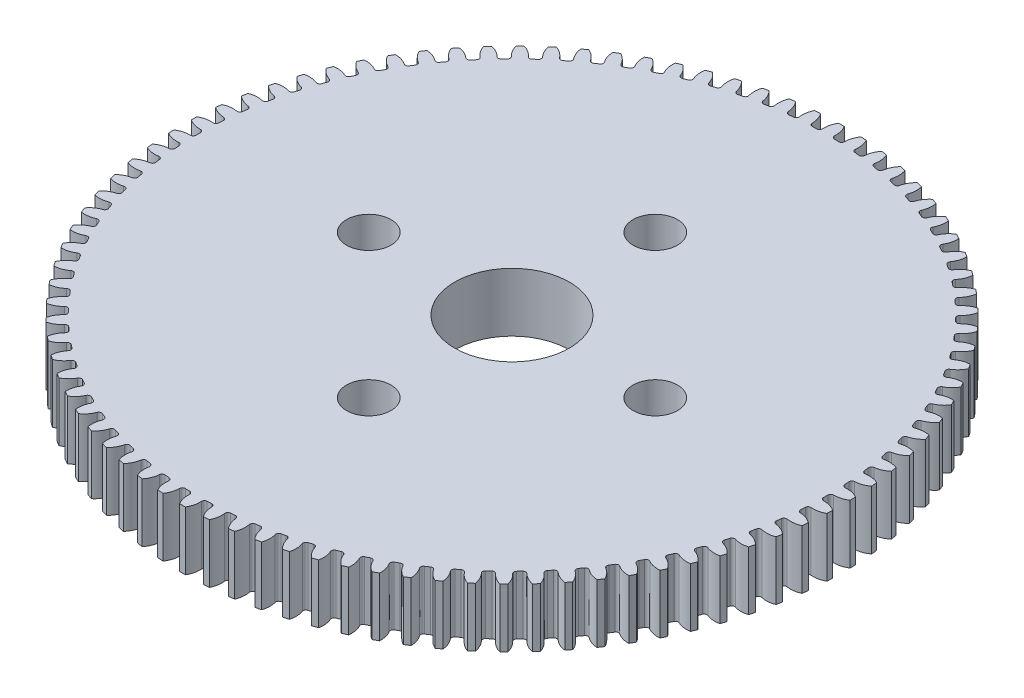
SolidWorks part; units mm, degrees
ref_plane "Front Plane" through (0, 0, 0) normal (0, 0, 1) x (1, 0, 0)
ref_plane "Top Plane" through (0, 0, 0) normal (0, 1, 0) x (1, 0, 0)
ref_plane "Right Plane" through (0, 0, 0) normal (1, 0, 0) x (0, 0, -1)
sketch "Sketch1" plane through (0, 0, 0) normal (0, 1, 0) x (1, 0, 0)
  line L0 (0, 0) -> (0, 23) construction
  line L2 (-0.1965, 23) -> (0.1965, 23)
  line L5 (1.4084, 22.9577) -> (1.8004, 22.9303)
  line L6 (3.0064, 22.8035) -> (3.3956, 22.7488)
  line L7 (4.5898, 22.5382) -> (4.9742, 22.4565)
  line L8 (6.1508, 22.1632) -> (6.5285, 22.0549)
  line L9 (7.6818, 21.6801) -> (8.0511, 21.5457)
  line L10 (9.1754, 21.0915) -> (9.5345, 20.9316)
  line L11 (10.6243, 20.4) -> (10.9713, 20.2155)
  line L12 (12.0215, 19.6092) -> (12.3548, 19.401)
  line L13 (13.3601, 18.7229) -> (13.678, 18.4919)
  line L14 (14.6336, 17.7453) -> (14.9346, 17.4927)
  line L15 (15.8358, 16.6813) -> (16.1185, 16.4083)
  line L16 (16.9608, 15.536) -> (17.2238, 15.244)
  line L17 (18.0033, 14.3151) -> (18.2452, 14.0054)
  line L18 (18.958, 13.0243) -> (19.1777, 12.6985)
  line L19 (19.8203, 11.6702) -> (20.0168, 11.3298)
  line L20 (20.5861, 10.2591) -> (20.7584, 9.9059)
  line L21 (21.2516, 8.7981) -> (21.3988, 8.4338)
  line L22 (21.8136, 7.2943) -> (21.935, 6.9205)
  line L23 (22.2693, 5.7549) -> (22.3643, 5.3735)
  line L24 (22.6165, 4.1874) -> (22.6847, 3.8004)
  line L25 (22.8535, 2.5996) -> (22.8945, 2.2087)
  line L26 (22.9791, 0.9991) -> (22.9928, 0.6063)
  line L27 (22.9928, -0.6063) -> (22.9791, -0.9991)
  line L28 (22.8945, -2.2087) -> (22.8535, -2.5996)
  line L29 (22.6847, -3.8004) -> (22.6165, -4.1874)
  line L30 (22.3643, -5.3735) -> (22.2693, -5.7549)
  line L31 (21.935, -6.9205) -> (21.8136, -7.2943)
  line L32 (21.3988, -8.4338) -> (21.2516, -8.7981)
  line L33 (20.7584, -9.9059) -> (20.5861, -10.2591)
  line L34 (20.0168, -11.3298) -> (19.8203, -11.6702)
  line L35 (19.1777, -12.6985) -> (18.958, -13.0243)
  line L36 (18.2452, -14.0054) -> (18.0033, -14.3151)
  line L37 (17.2238, -15.244) -> (16.9608, -15.536)
  line L38 (16.1185, -16.4083) -> (15.8358, -16.6813)
  line L39 (14.9346, -17.4927) -> (14.6336, -17.7453)
  line L40 (13.678, -18.4919) -> (13.3601, -18.7229)
  line L41 (12.3548, -19.401) -> (12.0215, -19.6092)
  line L42 (10.9713, -20.2155) -> (10.6243, -20.4)
  line L43 (9.5345, -20.9316) -> (9.1754, -21.0915)
  line L44 (8.0511, -21.5457) -> (7.6818, -21.6801)
  line L45 (6.5285, -22.0549) -> (6.1508, -22.1632)
  line L46 (4.9742, -22.4565) -> (4.5898, -22.5382)
  line L47 (3.3956, -22.7488) -> (3.0064, -22.8035)
  line L48 (1.8004, -22.9303) -> (1.4084, -22.9577)
  line L49 (0.1965, -23) -> (-0.1965, -23)
  line L50 (-1.4084, -22.9577) -> (-1.8004, -22.9303)
  line L51 (-3.0064, -22.8035) -> (-3.3956, -22.7488)
  line L52 (-4.5898, -22.5382) -> (-4.9742, -22.4565)
  line L53 (-6.1508, -22.1632) -> (-6.5285, -22.0549)
  line L54 (-7.6818, -21.6801) -> (-8.0511, -21.5457)
  line L55 (-9.1754, -21.0915) -> (-9.5345, -20.9316)
  line L56 (-10.6243, -20.4) -> (-10.9713, -20.2155)
  line L57 (-12.0215, -19.6092) -> (-12.3548, -19.401)
  line L58 (-13.3601, -18.7229) -> (-13.678, -18.4919)
  line L59 (-14.6336, -17.7453) -> (-14.9346, -17.4927)
  line L60 (-15.8358, -16.6813) -> (-16.1185, -16.4083)
  line L61 (-16.9608, -15.536) -> (-17.2238, -15.244)
  line L62 (-18.0033, -14.3151) -> (-18.2452, -14.0054)
  line L63 (-18.958, -13.0243) -> (-19.1777, -12.6985)
  line L64 (-19.8203, -11.6702) -> (-20.0168, -11.3298)
  line L65 (-20.5861, -10.2591) -> (-20.7584, -9.9059)
  line L66 (-21.2516, -8.7981) -> (-21.3988, -8.4338)
  line L67 (-21.8136, -7.2943) -> (-21.935, -6.9205)
  line L68 (-22.2693, -5.7549) -> (-22.3643, -5.3735)
  line L69 (-22.6165, -4.1874) -> (-22.6847, -3.8004)
  line L70 (-22.8535, -2.5996) -> (-22.8945, -2.2087)
  line L71 (-22.9791, -0.9991) -> (-22.9928, -0.6063)
  line L72 (-22.9928, 0.6063) -> (-22.9791, 0.9991)
  line L73 (-22.8945, 2.2087) -> (-22.8535, 2.5996)
  line L74 (-22.6847, 3.8004) -> (-22.6165, 4.1874)
  line L75 (-22.3643, 5.3735) -> (-22.2693, 5.7549)
  line L76 (-21.935, 6.9205) -> (-21.8136, 7.2943)
  line L77 (-21.3988, 8.4338) -> (-21.2516, 8.7981)
  line L78 (-20.7584, 9.9059) -> (-20.5861, 10.2591)
  line L79 (-20.0168, 11.3298) -> (-19.8203, 11.6702)
  line L80 (-19.1777, 12.6985) -> (-18.958, 13.0243)
  line L81 (-18.2452, 14.0054) -> (-18.0033, 14.3151)
  line L82 (-17.2238, 15.244) -> (-16.9608, 15.536)
  line L83 (-16.1185, 16.4083) -> (-15.8358, 16.6813)
  line L84 (-14.9346, 17.4927) -> (-14.6336, 17.7453)
  line L85 (-13.678, 18.4919) -> (-13.3601, 18.7229)
  line L86 (-12.3548, 19.401) -> (-12.0215, 19.6092)
  line L87 (-10.9713, 20.2155) -> (-10.6243, 20.4)
  line L88 (-9.5345, 20.9316) -> (-9.1754, 21.0915)
  line L89 (-8.0511, 21.5457) -> (-7.6818, 21.6801)
  line L90 (-6.5285, 22.0549) -> (-6.1508, 22.1632)
  line L91 (-4.9742, 22.4565) -> (-4.5898, 22.5382)
  line L92 (-3.3956, 22.7488) -> (-3.0064, 22.8035)
  line L93 (-1.8004, 22.9303) -> (-1.4084, 22.9577)
  circle A0 centre (0, 0) radius 22.5 construction
  circle A1 centre (0, 0) radius 4
  arc A3 (-0.6132, 21.8914) -> (-0.9154, 21.8809) centre (0, 0) ccw
  arc A4 (-0.4192, 22.1039) -> (-0.1965, 23) centre (1.1086, 22.2) cw
  arc A5 (0.4192, 22.1039) -> (0.1965, 23) centre (-1.1086, 22.2) ccw
  arc A6 (-0.4192, 22.1039) -> (-0.6132, 21.8914) centre (-0.6188, 22.0913) cw
  arc A7 (0.6132, 21.8914) -> (0.4192, 22.1039) centre (0.6188, 22.0913) cw
  arc A8 (1.1237, 22.0793) -> (1.4084, 22.9577) centre (2.6545, 22.0686) cw
  arc A9 (1.1237, 22.0793) -> (0.9154, 21.8809) centre (0.9238, 22.0807) cw
  arc A10 (2.1387, 21.7953) -> (1.96, 22.0208) centre (2.1583, 21.9944) cw
  arc A11 (1.96, 22.0208) -> (1.8004, 22.9303) centre (0.4427, 22.2233) ccw
  arc A12 (2.6612, 21.9471) -> (3.0064, 22.8035) centre (4.1874, 21.8297) cw
  arc A13 (2.6612, 21.9471) -> (2.4395, 21.7637) centre (2.4618, 21.9625) cw
  arc A14 (3.6539, 21.593) -> (3.4914, 21.8304) centre (3.6873, 21.7902) cw
  arc A15 (3.4914, 21.8304) -> (3.3956, 22.7488) centre (1.9919, 22.1382) ccw
  arc A16 (4.1857, 21.708) -> (4.5898, 22.5382) centre (5.7, 21.4844) cw
  arc A17 (4.1857, 21.708) -> (3.9517, 21.5405) centre (3.9878, 21.7372) cw
  arc A18 (5.1513, 21.2855) -> (5.0057, 21.5337) centre (5.1983, 21.4799) cw
  arc A19 (5.0057, 21.5337) -> (4.9742, 22.4565) centre (3.5313, 21.9454) ccw
  arc A20 (5.6897, 21.3632) -> (6.1508, 22.1632) centre (7.1848, 21.0344) cw
  arc A21 (5.6897, 21.3632) -> (5.4447, 21.2124) centre (5.4944, 21.4061) cw
  arc A22 (6.6235, 20.8744) -> (6.4956, 21.1321) centre (6.684, 21.065) cw
  arc A23 (6.4956, 21.1321) -> (6.5285, 22.0549) centre (5.0535, 21.6456) ccw
  arc A24 (7.1661, 20.9142) -> (7.6818, 21.6801) centre (8.6346, 20.482) cw
  arc A25 (7.1661, 20.9142) -> (6.9111, 20.7809) centre (6.9742, 20.9707) cw
  arc A26 (8.0635, 20.3615) -> (7.9539, 20.6275) centre (8.1371, 20.5474) cw
  arc A27 (7.9539, 20.6275) -> (8.0511, 21.5457) centre (6.5511, 21.2403) ccw
  arc A28 (8.6075, 20.3634) -> (9.1754, 21.0915) centre (10.0423, 19.8298) cw
  arc A29 (8.6075, 20.3634) -> (8.3439, 20.2482) centre (8.4201, 20.4331) cw
  arc A30 (9.4642, 19.7494) -> (9.3734, 20.0224) centre (9.5506, 19.9298) cw
  arc A31 (9.3734, 20.0224) -> (9.5345, 20.9316) centre (8.0168, 20.7316) ccw
  arc A32 (10.007, 19.7134) -> (10.6243, 20.4) centre (11.4011, 19.081) cw
  arc A33 (10.007, 19.7134) -> (9.736, 19.6168) centre (9.8249, 19.796) cw
  arc A34 (10.8188, 19.0411) -> (10.7473, 19.3198) centre (10.9176, 19.215) cw
  arc A35 (10.7473, 19.3198) -> (10.9713, 20.2155) centre (9.4435, 20.1219) ccw
  arc A36 (11.3578, 18.9673) -> (12.0215, 19.6092) centre (12.7043, 18.2392) cw
  arc A37 (11.3578, 18.9673) -> (11.0807, 18.8899) centre (11.1819, 19.0624) cw
  arc A38 (12.1207, 18.24) -> (12.0688, 18.523) centre (12.2314, 18.4066) cw
  arc A39 (12.0688, 18.523) -> (12.3548, 19.401) centre (10.8241, 19.4141) ccw
  arc A40 (12.6532, 18.1288) -> (13.3601, 18.7229) centre (13.9457, 17.3086) cw
  arc A41 (12.6532, 18.1288) -> (12.3714, 18.0709) centre (12.4844, 18.236) cw
  arc A42 (13.3635, 17.3501) -> (13.3315, 17.636) centre (13.4856, 17.5086) cw
  arc A43 (13.3315, 17.636) -> (13.678, 18.4919) centre (12.152, 18.6118) ccw
  arc A44 (13.887, 17.202) -> (14.6336, 17.7453) centre (15.1191, 16.2936) cw
  arc A45 (13.887, 17.202) -> (13.6018, 17.1639) centre (13.726, 17.3207) cw
  arc A46 (14.5412, 16.3757) -> (14.5292, 16.6631) centre (14.674, 16.5252) cw
  arc A47 (14.5292, 16.6631) -> (14.9346, 17.4927) centre (13.4207, 17.7188) ccw
  arc A48 (15.0531, 16.1914) -> (15.8358, 16.6813) centre (16.2188, 15.1993) cw
  arc A49 (15.0531, 16.1914) -> (14.766, 16.1733) centre (14.9008, 16.321) cw
  arc A50 (15.6481, 15.3214) -> (15.6562, 15.609) centre (15.791, 15.4613) cw
  arc A51 (15.6562, 15.609) -> (16.1185, 16.4083) centre (14.624, 16.7394) ccw
  arc A52 (16.1459, 15.1019) -> (16.9608, 15.536) centre (17.2396, 14.0309) cw
  arc A53 (16.1459, 15.1019) -> (15.8582, 15.1039) centre (16.003, 15.2418) cw
  arc A54 (16.6788, 14.1925) -> (16.7069, 14.4789) centre (16.8311, 14.3222) cw
  arc A55 (16.7069, 14.4789) -> (17.2238, 15.244) centre (15.756, 15.6785) ccw
  arc A56 (17.16, 13.9388) -> (18.0033, 14.3151) centre (18.1763, 12.7941) cw
  arc A57 (17.16, 13.9388) -> (16.8732, 13.9609) centre (17.0273, 14.0884) cw
  arc A58 (17.6282, 12.9945) -> (17.6762, 13.2782) centre (17.7892, 13.1132) cw
  arc A59 (17.6762, 13.2782) -> (18.2452, 14.0054) centre (16.8113, 14.5412) ccw
  arc A60 (18.0906, 12.7078) -> (18.958, 13.0243) centre (19.0245, 11.495) cw
  arc A61 (18.0906, 12.7078) -> (17.8059, 12.7499) centre (17.9685, 12.8663) cw
  arc A62 (18.4917, 11.7332) -> (18.5594, 12.0128) centre (18.6606, 11.8403) cw
  arc A63 (18.5594, 12.0128) -> (19.1777, 12.6985) centre (17.7847, 13.3331) ccw
  arc A64 (18.933, 11.415) -> (19.8203, 11.6702) centre (19.78, 10.14) cw
  arc A65 (18.933, 11.415) -> (18.6519, 11.4767) centre (18.8223, 11.5815) cw
  arc A66 (19.2651, 10.4147) -> (19.3521, 10.6889) centre (19.441, 10.5098) cw
  arc A67 (19.3521, 10.6889) -> (20.0168, 11.3298) centre (18.6715, 12.06) ccw
  arc A68 (19.6831, 10.0665) -> (20.5861, 10.2591) centre (20.4392, 8.7355) cw
  arc A69 (19.6831, 10.0665) -> (19.4071, 10.1477) centre (19.5843, 10.2404) cw
  arc A70 (19.9447, 9.0455) -> (20.0506, 9.313) centre (20.1268, 9.1281) cw
  arc A71 (20.0506, 9.313) -> (20.7584, 9.9059) centre (19.4673, 10.7282) ccw
  arc A72 (20.3374, 8.6689) -> (21.2516, 8.7981) centre (20.9988, 7.2884) cw
  arc A73 (20.3374, 8.6689) -> (20.0677, 8.7692) centre (20.2509, 8.8493) cw
  arc A74 (20.5271, 7.6321) -> (20.6514, 7.8916) centre (20.7145, 7.7018) cw
  arc A75 (20.6514, 7.8916) -> (21.3988, 8.4338) centre (20.1682, 9.3441) ccw
  arc A76 (20.8925, 7.2291) -> (21.8136, 7.2943) centre (21.456, 5.8059) cw
  arc A77 (20.8925, 7.2291) -> (20.6305, 7.348) centre (20.8189, 7.4151) cw
  arc A78 (21.0095, 6.1817) -> (21.1516, 6.4318) centre (21.2013, 6.2381) cw
  arc A79 (21.1516, 6.4318) -> (21.935, 6.9205) centre (20.7709, 7.9145) ccw
  arc A80 (21.3459, 5.7541) -> (22.2693, 5.7549) centre (21.8088, 4.295) cw
  arc A81 (21.3459, 5.7541) -> (21.0928, 5.891) centre (21.2854, 5.9448) cw
  arc A82 (21.3895, 4.7011) -> (21.5487, 4.9407) centre (21.5848, 4.744) cw
  arc A83 (21.5487, 4.9407) -> (22.3643, 5.3735) centre (21.2724, 6.4463) ccw
  arc A84 (21.6953, 4.2511) -> (22.6165, 4.1874) centre (22.0552, 2.7633) cw
  arc A85 (21.6953, 4.2511) -> (21.4524, 4.4053) centre (21.6483, 4.4455) cw
  arc A86 (21.6653, 3.1975) -> (21.8409, 3.4255) centre (21.8632, 3.2268) cw
  arc A87 (21.8409, 3.4255) -> (22.6847, 3.8004) centre (21.6702, 4.9467) ccw
  arc A88 (21.939, 2.7274) -> (22.8535, 2.5996) centre (22.1943, 1.218) cw
  arc A89 (21.939, 2.7274) -> (21.7074, 2.8981) centre (21.9056, 2.9246) cw
  arc A90 (21.8356, 1.6785) -> (22.0266, 1.8936) centre (22.035, 1.6938) cw
  arc A91 (22.0266, 1.8936) -> (22.8945, 2.2087) centre (21.9625, 3.423) ccw
  arc A92 (22.0758, 1.1903) -> (22.9791, 0.9991) centre (22.2252, -0.3331) cw
  arc A93 (22.0758, 1.1903) -> (21.8567, 1.3768) centre (22.0563, 1.3894) cw
  arc A94 (21.8995, 0.1512) -> (22.1051, 0.3525) centre (22.0995, 0.1526) cw
  arc A95 (22.1051, 0.3525) -> (22.9928, 0.6063) centre (22.1478, 1.8827) ccw
  arc A96 (22.1051, -0.3525) -> (22.9928, -0.6063) centre (22.1478, -1.8827) cw
  arc A97 (22.1051, -0.3525) -> (21.8995, -0.1512) centre (22.0995, -0.1526) cw
  arc A98 (21.8567, -1.3768) -> (22.0758, -1.1903) centre (22.0563, -1.3894) cw
  arc A99 (22.0758, -1.1903) -> (22.9791, -0.9991) centre (22.2252, 0.3331) ccw
  arc A100 (22.0266, -1.8936) -> (22.8945, -2.2087) centre (21.9625, -3.423) cw
  arc A101 (22.0266, -1.8936) -> (21.8356, -1.6785) centre (22.035, -1.6938) cw
  arc A102 (21.7074, -2.8981) -> (21.939, -2.7274) centre (21.9056, -2.9246) cw
  arc A103 (21.939, -2.7274) -> (22.8535, -2.5996) centre (22.1943, -1.218) ccw
  arc A104 (21.8409, -3.4255) -> (22.6847, -3.8004) centre (21.6702, -4.9467) cw
  arc A105 (21.8409, -3.4255) -> (21.6653, -3.1975) centre (21.8632, -3.2268) cw
  arc A106 (21.4524, -4.4053) -> (21.6953, -4.2511) centre (21.6483, -4.4455) cw
  arc A107 (21.6953, -4.2511) -> (22.6165, -4.1874) centre (22.0552, -2.7633) ccw
  arc A108 (21.5487, -4.9407) -> (22.3643, -5.3735) centre (21.2724, -6.4463) cw
  arc A109 (21.5487, -4.9407) -> (21.3895, -4.7011) centre (21.5848, -4.744) cw
  arc A110 (21.0928, -5.891) -> (21.3459, -5.7541) centre (21.2854, -5.9448) cw
  arc A111 (21.3459, -5.7541) -> (22.2693, -5.7549) centre (21.8088, -4.295) ccw
  arc A112 (21.1516, -6.4318) -> (21.935, -6.9205) centre (20.7709, -7.9145) cw
  arc A113 (21.1516, -6.4318) -> (21.0095, -6.1817) centre (21.2013, -6.2381) cw
  arc A114 (20.6305, -7.348) -> (20.8925, -7.2291) centre (20.8189, -7.4151) cw
  arc A115 (20.8925, -7.2291) -> (21.8136, -7.2943) centre (21.456, -5.8059) ccw
  arc A116 (20.6514, -7.8916) -> (21.3988, -8.4338) centre (20.1682, -9.3441) cw
  arc A117 (20.6514, -7.8916) -> (20.5271, -7.6321) centre (20.7145, -7.7018) cw
  arc A118 (20.0677, -8.7692) -> (20.3374, -8.6689) centre (20.2509, -8.8493) cw
  arc A119 (20.3374, -8.6689) -> (21.2516, -8.7981) centre (20.9988, -7.2884) ccw
  arc A120 (20.0506, -9.313) -> (20.7584, -9.9059) centre (19.4673, -10.7282) cw
  arc A121 (20.0506, -9.313) -> (19.9447, -9.0455) centre (20.1268, -9.1281) cw
  arc A122 (19.4071, -10.1477) -> (19.6831, -10.0665) centre (19.5843, -10.2404) cw
  arc A123 (19.6831, -10.0665) -> (20.5861, -10.2591) centre (20.4392, -8.7355) ccw
  arc A124 (19.3521, -10.6889) -> (20.0168, -11.3298) centre (18.6715, -12.06) cw
  arc A125 (19.3521, -10.6889) -> (19.2651, -10.4147) centre (19.441, -10.5098) cw
  arc A126 (18.6519, -11.4767) -> (18.933, -11.415) centre (18.8223, -11.5815) cw
  arc A127 (18.933, -11.415) -> (19.8203, -11.6702) centre (19.78, -10.14) ccw
  arc A128 (18.5594, -12.0128) -> (19.1777, -12.6985) centre (17.7847, -13.3331) cw
  arc A129 (18.5594, -12.0128) -> (18.4917, -11.7332) centre (18.6606, -11.8403) cw
  arc A130 (17.8059, -12.7499) -> (18.0906, -12.7078) centre (17.9685, -12.8663) cw
  arc A131 (18.0906, -12.7078) -> (18.958, -13.0243) centre (19.0245, -11.495) ccw
  arc A132 (17.6762, -13.2782) -> (18.2452, -14.0054) centre (16.8113, -14.5412) cw
  arc A133 (17.6762, -13.2782) -> (17.6282, -12.9945) centre (17.7892, -13.1132) cw
  arc A134 (16.8732, -13.9609) -> (17.16, -13.9388) centre (17.0273, -14.0884) cw
  arc A135 (17.16, -13.9388) -> (18.0033, -14.3151) centre (18.1763, -12.7941) ccw
  arc A136 (16.7069, -14.4789) -> (17.2238, -15.244) centre (15.756, -15.6785) cw
  arc A137 (16.7069, -14.4789) -> (16.6788, -14.1925) centre (16.8311, -14.3222) cw
  arc A138 (15.8582, -15.1039) -> (16.1459, -15.1019) centre (16.003, -15.2418) cw
  arc A139 (16.1459, -15.1019) -> (16.9608, -15.536) centre (17.2396, -14.0309) ccw
  arc A140 (15.6562, -15.609) -> (16.1185, -16.4083) centre (14.624, -16.7394) cw
  arc A141 (15.6562, -15.609) -> (15.6481, -15.3214) centre (15.791, -15.4613) cw
  arc A142 (14.766, -16.1733) -> (15.0531, -16.1914) centre (14.9008, -16.321) cw
  arc A143 (15.0531, -16.1914) -> (15.8358, -16.6813) centre (16.2188, -15.1993) ccw
  arc A144 (14.5292, -16.6631) -> (14.9346, -17.4927) centre (13.4207, -17.7188) cw
  arc A145 (14.5292, -16.6631) -> (14.5412, -16.3757) centre (14.674, -16.5252) cw
  arc A146 (13.6018, -17.1639) -> (13.887, -17.202) centre (13.726, -17.3207) cw
  arc A147 (13.887, -17.202) -> (14.6336, -17.7453) centre (15.1191, -16.2936) ccw
  arc A148 (13.3315, -17.636) -> (13.678, -18.4919) centre (12.152, -18.6118) cw
  arc A149 (13.3315, -17.636) -> (13.3635, -17.3501) centre (13.4856, -17.5086) cw
  arc A150 (12.3714, -18.0709) -> (12.6532, -18.1288) centre (12.4844, -18.236) cw
  arc A151 (12.6532, -18.1288) -> (13.3601, -18.7229) centre (13.9457, -17.3086) ccw
  arc A152 (12.0688, -18.523) -> (12.3548, -19.401) centre (10.8241, -19.4141) cw
  arc A153 (12.0688, -18.523) -> (12.1207, -18.24) centre (12.2314, -18.4066) cw
  arc A154 (11.0807, -18.8899) -> (11.3578, -18.9673) centre (11.1819, -19.0624) cw
  arc A155 (11.3578, -18.9673) -> (12.0215, -19.6092) centre (12.7043, -18.2392) ccw
  arc A156 (10.7473, -19.3198) -> (10.9713, -20.2155) centre (9.4435, -20.1219) cw
  arc A157 (10.7473, -19.3198) -> (10.8188, -19.0411) centre (10.9176, -19.215) cw
  arc A158 (9.736, -19.6168) -> (10.007, -19.7134) centre (9.8249, -19.796) cw
  arc A159 (10.007, -19.7134) -> (10.6243, -20.4) centre (11.4011, -19.081) ccw
  arc A160 (9.3734, -20.0224) -> (9.5345, -20.9316) centre (8.0168, -20.7316) cw
  arc A161 (9.3734, -20.0224) -> (9.4642, -19.7494) centre (9.5506, -19.9298) cw
  arc A162 (8.3439, -20.2482) -> (8.6075, -20.3634) centre (8.4201, -20.4331) cw
  arc A163 (8.6075, -20.3634) -> (9.1754, -21.0915) centre (10.0423, -19.8298) ccw
  arc A164 (7.9539, -20.6275) -> (8.0511, -21.5457) centre (6.5511, -21.2403) cw
  arc A165 (7.9539, -20.6275) -> (8.0635, -20.3615) centre (8.1371, -20.5474) cw
  arc A166 (6.9111, -20.7809) -> (7.1661, -20.9142) centre (6.9742, -20.9707) cw
  arc A167 (7.1661, -20.9142) -> (7.6818, -21.6801) centre (8.6346, -20.482) ccw
  arc A168 (6.4956, -21.1321) -> (6.5285, -22.0549) centre (5.0535, -21.6456) cw
  arc A169 (6.4956, -21.1321) -> (6.6235, -20.8744) centre (6.684, -21.065) cw
  arc A170 (5.4447, -21.2124) -> (5.6897, -21.3632) centre (5.4944, -21.4061) cw
  arc A171 (5.6897, -21.3632) -> (6.1508, -22.1632) centre (7.1848, -21.0344) ccw
  arc A172 (5.0057, -21.5337) -> (4.9742, -22.4565) centre (3.5313, -21.9454) cw
  arc A173 (5.0057, -21.5337) -> (5.1513, -21.2855) centre (5.1983, -21.4799) cw
  arc A174 (3.9517, -21.5405) -> (4.1857, -21.708) centre (3.9878, -21.7372) cw
  arc A175 (4.1857, -21.708) -> (4.5898, -22.5382) centre (5.7, -21.4844) ccw
  arc A176 (3.4914, -21.8304) -> (3.3956, -22.7488) centre (1.9919, -22.1382) cw
  arc A177 (3.4914, -21.8304) -> (3.6539, -21.593) centre (3.6873, -21.7902) cw
  arc A178 (2.4395, -21.7637) -> (2.6612, -21.9471) centre (2.4618, -21.9625) cw
  arc A179 (2.6612, -21.9471) -> (3.0064, -22.8035) centre (4.1874, -21.8297) ccw
  arc A180 (1.96, -22.0208) -> (1.8004, -22.9303) centre (0.4427, -22.2233) cw
  arc A181 (1.96, -22.0208) -> (2.1387, -21.7953) centre (2.1583, -21.9944) cw
  arc A182 (0.9154, -21.8809) -> (1.1237, -22.0793) centre (0.9238, -22.0807) cw
  arc A183 (1.1237, -22.0793) -> (1.4084, -22.9577) centre (2.6545, -22.0686) ccw
  arc A184 (0.4192, -22.1039) -> (0.1965, -23) centre (-1.1086, -22.2) cw
  arc A185 (0.4192, -22.1039) -> (0.6132, -21.8914) centre (0.6188, -22.0913) cw
  arc A186 (-0.6132, -21.8914) -> (-0.4192, -22.1039) centre (-0.6188, -22.0913) cw
  arc A187 (-0.4192, -22.1039) -> (-0.1965, -23) centre (1.1086, -22.2) ccw
  arc A188 (-1.1237, -22.0793) -> (-1.4084, -22.9577) centre (-2.6545, -22.0686) cw
  arc A189 (-1.1237, -22.0793) -> (-0.9154, -21.8809) centre (-0.9238, -22.0807) cw
  arc A190 (-2.1387, -21.7953) -> (-1.96, -22.0208) centre (-2.1583, -21.9944) cw
  arc A191 (-1.96, -22.0208) -> (-1.8004, -22.9303) centre (-0.4427, -22.2233) ccw
  arc A192 (-2.6612, -21.9471) -> (-3.0064, -22.8035) centre (-4.1874, -21.8297) cw
  arc A193 (-2.6612, -21.9471) -> (-2.4395, -21.7637) centre (-2.4618, -21.9625) cw
  arc A194 (-3.6539, -21.593) -> (-3.4914, -21.8304) centre (-3.6873, -21.7902) cw
  arc A195 (-3.4914, -21.8304) -> (-3.3956, -22.7488) centre (-1.9919, -22.1382) ccw
  arc A196 (-4.1857, -21.708) -> (-4.5898, -22.5382) centre (-5.7, -21.4844) cw
  arc A197 (-4.1857, -21.708) -> (-3.9517, -21.5405) centre (-3.9878, -21.7372) cw
  arc A198 (-5.1513, -21.2855) -> (-5.0057, -21.5337) centre (-5.1983, -21.4799) cw
  arc A199 (-5.0057, -21.5337) -> (-4.9742, -22.4565) centre (-3.5313, -21.9454) ccw
  arc A200 (-5.6897, -21.3632) -> (-6.1508, -22.1632) centre (-7.1848, -21.0344) cw
  arc A201 (-5.6897, -21.3632) -> (-5.4447, -21.2124) centre (-5.4944, -21.4061) cw
  arc A202 (-6.6235, -20.8744) -> (-6.4956, -21.1321) centre (-6.684, -21.065) cw
  arc A203 (-6.4956, -21.1321) -> (-6.5285, -22.0549) centre (-5.0535, -21.6456) ccw
  arc A204 (-7.1661, -20.9142) -> (-7.6818, -21.6801) centre (-8.6346, -20.482) cw
  arc A205 (-7.1661, -20.9142) -> (-6.9111, -20.7809) centre (-6.9742, -20.9707) cw
  arc A206 (-8.0635, -20.3615) -> (-7.9539, -20.6275) centre (-8.1371, -20.5474) cw
  arc A207 (-7.9539, -20.6275) -> (-8.0511, -21.5457) centre (-6.5511, -21.2403) ccw
  arc A208 (-8.6075, -20.3634) -> (-9.1754, -21.0915) centre (-10.0423, -19.8298) cw
  arc A209 (-8.6075, -20.3634) -> (-8.3439, -20.2482) centre (-8.4201, -20.4331) cw
  arc A210 (-9.4642, -19.7494) -> (-9.3734, -20.0224) centre (-9.5506, -19.9298) cw
  arc A211 (-9.3734, -20.0224) -> (-9.5345, -20.9316) centre (-8.0168, -20.7316) ccw
  arc A212 (-10.007, -19.7134) -> (-10.6243, -20.4) centre (-11.4011, -19.081) cw
  arc A213 (-10.007, -19.7134) -> (-9.736, -19.6168) centre (-9.8249, -19.796) cw
  arc A214 (-10.8188, -19.0411) -> (-10.7473, -19.3198) centre (-10.9176, -19.215) cw
  arc A215 (-10.7473, -19.3198) -> (-10.9713, -20.2155) centre (-9.4435, -20.1219) ccw
  arc A216 (-11.3578, -18.9673) -> (-12.0215, -19.6092) centre (-12.7043, -18.2392) cw
  arc A217 (-11.3578, -18.9673) -> (-11.0807, -18.8899) centre (-11.1819, -19.0624) cw
  arc A218 (-12.1207, -18.24) -> (-12.0688, -18.523) centre (-12.2314, -18.4066) cw
  arc A219 (-12.0688, -18.523) -> (-12.3548, -19.401) centre (-10.8241, -19.4141) ccw
  arc A220 (-12.6532, -18.1288) -> (-13.3601, -18.7229) centre (-13.9457, -17.3086) cw
  arc A221 (-12.6532, -18.1288) -> (-12.3714, -18.0709) centre (-12.4844, -18.236) cw
  arc A222 (-13.3635, -17.3501) -> (-13.3315, -17.636) centre (-13.4856, -17.5086) cw
  arc A223 (-13.3315, -17.636) -> (-13.678, -18.4919) centre (-12.152, -18.6118) ccw
  arc A224 (-13.887, -17.202) -> (-14.6336, -17.7453) centre (-15.1191, -16.2936) cw
  arc A225 (-13.887, -17.202) -> (-13.6018, -17.1639) centre (-13.726, -17.3207) cw
  arc A226 (-14.5412, -16.3757) -> (-14.5292, -16.6631) centre (-14.674, -16.5252) cw
  arc A227 (-14.5292, -16.6631) -> (-14.9346, -17.4927) centre (-13.4207, -17.7188) ccw
  arc A228 (-15.0531, -16.1914) -> (-15.8358, -16.6813) centre (-16.2188, -15.1993) cw
  arc A229 (-15.0531, -16.1914) -> (-14.766, -16.1733) centre (-14.9008, -16.321) cw
  arc A230 (-15.6481, -15.3214) -> (-15.6562, -15.609) centre (-15.791, -15.4613) cw
  arc A231 (-15.6562, -15.609) -> (-16.1185, -16.4083) centre (-14.624, -16.7394) ccw
  arc A232 (-16.1459, -15.1019) -> (-16.9608, -15.536) centre (-17.2396, -14.0309) cw
  arc A233 (-16.1459, -15.1019) -> (-15.8582, -15.1039) centre (-16.003, -15.2418) cw
  arc A234 (-16.6788, -14.1925) -> (-16.7069, -14.4789) centre (-16.8311, -14.3222) cw
  arc A235 (-16.7069, -14.4789) -> (-17.2238, -15.244) centre (-15.756, -15.6785) ccw
  arc A236 (-17.16, -13.9388) -> (-18.0033, -14.3151) centre (-18.1763, -12.7941) cw
  arc A237 (-17.16, -13.9388) -> (-16.8732, -13.9609) centre (-17.0273, -14.0884) cw
  arc A238 (-17.6282, -12.9945) -> (-17.6762, -13.2782) centre (-17.7892, -13.1132) cw
  arc A239 (-17.6762, -13.2782) -> (-18.2452, -14.0054) centre (-16.8113, -14.5412) ccw
  arc A240 (-18.0906, -12.7078) -> (-18.958, -13.0243) centre (-19.0245, -11.495) cw
  arc A241 (-18.0906, -12.7078) -> (-17.8059, -12.7499) centre (-17.9685, -12.8663) cw
  arc A242 (-18.4917, -11.7332) -> (-18.5594, -12.0128) centre (-18.6606, -11.8403) cw
  arc A243 (-18.5594, -12.0128) -> (-19.1777, -12.6985) centre (-17.7847, -13.3331) ccw
  arc A244 (-18.933, -11.415) -> (-19.8203, -11.6702) centre (-19.78, -10.14) cw
  arc A245 (-18.933, -11.415) -> (-18.6519, -11.4767) centre (-18.8223, -11.5815) cw
  arc A246 (-19.2651, -10.4147) -> (-19.3521, -10.6889) centre (-19.441, -10.5098) cw
  arc A247 (-19.3521, -10.6889) -> (-20.0168, -11.3298) centre (-18.6715, -12.06) ccw
  arc A248 (-19.6831, -10.0665) -> (-20.5861, -10.2591) centre (-20.4392, -8.7355) cw
  arc A249 (-19.6831, -10.0665) -> (-19.4071, -10.1477) centre (-19.5843, -10.2404) cw
  arc A250 (-19.9447, -9.0455) -> (-20.0506, -9.313) centre (-20.1268, -9.1281) cw
  arc A251 (-20.0506, -9.313) -> (-20.7584, -9.9059) centre (-19.4673, -10.7282) ccw
  arc A252 (-20.3374, -8.6689) -> (-21.2516, -8.7981) centre (-20.9988, -7.2884) cw
  arc A253 (-20.3374, -8.6689) -> (-20.0677, -8.7692) centre (-20.2509, -8.8493) cw
  arc A254 (-20.5271, -7.6321) -> (-20.6514, -7.8916) centre (-20.7145, -7.7018) cw
  arc A255 (-20.6514, -7.8916) -> (-21.3988, -8.4338) centre (-20.1682, -9.3441) ccw
  arc A256 (-20.8925, -7.2291) -> (-21.8136, -7.2943) centre (-21.456, -5.8059) cw
  arc A257 (-20.8925, -7.2291) -> (-20.6305, -7.348) centre (-20.8189, -7.4151) cw
  arc A258 (-21.0095, -6.1817) -> (-21.1516, -6.4318) centre (-21.2013, -6.2381) cw
  arc A259 (-21.1516, -6.4318) -> (-21.935, -6.9205) centre (-20.7709, -7.9145) ccw
  arc A260 (-21.3459, -5.7541) -> (-22.2693, -5.7549) centre (-21.8088, -4.295) cw
  arc A261 (-21.3459, -5.7541) -> (-21.0928, -5.891) centre (-21.2854, -5.9448) cw
  arc A262 (-21.3895, -4.7011) -> (-21.5487, -4.9407) centre (-21.5848, -4.744) cw
  arc A263 (-21.5487, -4.9407) -> (-22.3643, -5.3735) centre (-21.2724, -6.4463) ccw
  arc A264 (-21.6953, -4.2511) -> (-22.6165, -4.1874) centre (-22.0552, -2.7633) cw
  arc A265 (-21.6953, -4.2511) -> (-21.4524, -4.4053) centre (-21.6483, -4.4455) cw
  arc A266 (-21.6653, -3.1975) -> (-21.8409, -3.4255) centre (-21.8632, -3.2268) cw
  arc A267 (-21.8409, -3.4255) -> (-22.6847, -3.8004) centre (-21.6702, -4.9467) ccw
  arc A268 (-21.939, -2.7274) -> (-22.8535, -2.5996) centre (-22.1943, -1.218) cw
  arc A269 (-21.939, -2.7274) -> (-21.7074, -2.8981) centre (-21.9056, -2.9246) cw
  arc A270 (-21.8356, -1.6785) -> (-22.0266, -1.8936) centre (-22.035, -1.6938) cw
  arc A271 (-22.0266, -1.8936) -> (-22.8945, -2.2087) centre (-21.9625, -3.423) ccw
  arc A272 (-22.0758, -1.1903) -> (-22.9791, -0.9991) centre (-22.2252, 0.3331) cw
  arc A273 (-22.0758, -1.1903) -> (-21.8567, -1.3768) centre (-22.0563, -1.3894) cw
  arc A274 (-21.8995, -0.1512) -> (-22.1051, -0.3525) centre (-22.0995, -0.1526) cw
  arc A275 (-22.1051, -0.3525) -> (-22.9928, -0.6063) centre (-22.1478, -1.8827) ccw
  arc A276 (-22.1051, 0.3525) -> (-22.9928, 0.6063) centre (-22.1478, 1.8827) cw
  arc A277 (-22.1051, 0.3525) -> (-21.8995, 0.1512) centre (-22.0995, 0.1526) cw
  arc A278 (-21.8567, 1.3768) -> (-22.0758, 1.1903) centre (-22.0563, 1.3894) cw
  arc A279 (-22.0758, 1.1903) -> (-22.9791, 0.9991) centre (-22.2252, -0.3331) ccw
  arc A280 (-22.0266, 1.8936) -> (-22.8945, 2.2087) centre (-21.9625, 3.423) cw
  arc A281 (-22.0266, 1.8936) -> (-21.8356, 1.6785) centre (-22.035, 1.6938) cw
  arc A282 (-21.7074, 2.8981) -> (-21.939, 2.7274) centre (-21.9056, 2.9246) cw
  arc A283 (-21.939, 2.7274) -> (-22.8535, 2.5996) centre (-22.1943, 1.218) ccw
  arc A284 (-21.8409, 3.4255) -> (-22.6847, 3.8004) centre (-21.6702, 4.9467) cw
  arc A285 (-21.8409, 3.4255) -> (-21.6653, 3.1975) centre (-21.8632, 3.2268) cw
  arc A286 (-21.4524, 4.4053) -> (-21.6953, 4.2511) centre (-21.6483, 4.4455) cw
  arc A287 (-21.6953, 4.2511) -> (-22.6165, 4.1874) centre (-22.0552, 2.7633) ccw
  arc A288 (-21.5487, 4.9407) -> (-22.3643, 5.3735) centre (-21.2724, 6.4463) cw
  arc A289 (-21.5487, 4.9407) -> (-21.3895, 4.7011) centre (-21.5848, 4.744) cw
  arc A290 (-21.0928, 5.891) -> (-21.3459, 5.7541) centre (-21.2854, 5.9448) cw
  arc A291 (-21.3459, 5.7541) -> (-22.2693, 5.7549) centre (-21.8088, 4.295) ccw
  arc A292 (-21.1516, 6.4318) -> (-21.935, 6.9205) centre (-20.7709, 7.9145) cw
  arc A293 (-21.1516, 6.4318) -> (-21.0095, 6.1817) centre (-21.2013, 6.2381) cw
  arc A294 (-20.6305, 7.348) -> (-20.8925, 7.2291) centre (-20.8189, 7.4151) cw
  arc A295 (-20.8925, 7.2291) -> (-21.8136, 7.2943) centre (-21.456, 5.8059) ccw
  arc A296 (-20.6514, 7.8916) -> (-21.3988, 8.4338) centre (-20.1682, 9.3441) cw
  arc A297 (-20.6514, 7.8916) -> (-20.5271, 7.6321) centre (-20.7145, 7.7018) cw
  arc A298 (-20.0677, 8.7692) -> (-20.3374, 8.6689) centre (-20.2509, 8.8493) cw
  arc A299 (-20.3374, 8.6689) -> (-21.2516, 8.7981) centre (-20.9988, 7.2884) ccw
  arc A300 (-20.0506, 9.313) -> (-20.7584, 9.9059) centre (-19.4673, 10.7282) cw
  arc A301 (-20.0506, 9.313) -> (-19.9447, 9.0455) centre (-20.1268, 9.1281) cw
  arc A302 (-19.4071, 10.1477) -> (-19.6831, 10.0665) centre (-19.5843, 10.2404) cw
  arc A303 (-19.6831, 10.0665) -> (-20.5861, 10.2591) centre (-20.4392, 8.7355) ccw
  arc A304 (-19.3521, 10.6889) -> (-20.0168, 11.3298) centre (-18.6715, 12.06) cw
  arc A305 (-19.3521, 10.6889) -> (-19.2651, 10.4147) centre (-19.441, 10.5098) cw
  arc A306 (-18.6519, 11.4767) -> (-18.933, 11.415) centre (-18.8223, 11.5815) cw
  arc A307 (-18.933, 11.415) -> (-19.8203, 11.6702) centre (-19.78, 10.14) ccw
  arc A308 (-18.5594, 12.0128) -> (-19.1777, 12.6985) centre (-17.7847, 13.3331) cw
  arc A309 (-18.5594, 12.0128) -> (-18.4917, 11.7332) centre (-18.6606, 11.8403) cw
  arc A310 (-17.8059, 12.7499) -> (-18.0906, 12.7078) centre (-17.9685, 12.8663) cw
  arc A311 (-18.0906, 12.7078) -> (-18.958, 13.0243) centre (-19.0245, 11.495) ccw
  arc A312 (-17.6762, 13.2782) -> (-18.2452, 14.0054) centre (-16.8113, 14.5412) cw
  arc A313 (-17.6762, 13.2782) -> (-17.6282, 12.9945) centre (-17.7892, 13.1132) cw
  arc A314 (-16.8732, 13.9609) -> (-17.16, 13.9388) centre (-17.0273, 14.0884) cw
  arc A315 (-17.16, 13.9388) -> (-18.0033, 14.3151) centre (-18.1763, 12.7941) ccw
  arc A316 (-16.7069, 14.4789) -> (-17.2238, 15.244) centre (-15.756, 15.6785) cw
  arc A317 (-16.7069, 14.4789) -> (-16.6788, 14.1925) centre (-16.8311, 14.3222) cw
  arc A318 (-15.8582, 15.1039) -> (-16.1459, 15.1019) centre (-16.003, 15.2418) cw
  arc A319 (-16.1459, 15.1019) -> (-16.9608, 15.536) centre (-17.2396, 14.0309) ccw
  arc A320 (-15.6562, 15.609) -> (-16.1185, 16.4083) centre (-14.624, 16.7394) cw
  arc A321 (-15.6562, 15.609) -> (-15.6481, 15.3214) centre (-15.791, 15.4613) cw
  arc A322 (-14.766, 16.1733) -> (-15.0531, 16.1914) centre (-14.9008, 16.321) cw
  arc A323 (-15.0531, 16.1914) -> (-15.8358, 16.6813) centre (-16.2188, 15.1993) ccw
  arc A324 (-14.5292, 16.6631) -> (-14.9346, 17.4927) centre (-13.4207, 17.7188) cw
  arc A325 (-14.5292, 16.6631) -> (-14.5412, 16.3757) centre (-14.674, 16.5252) cw
  arc A326 (-13.6018, 17.1639) -> (-13.887, 17.202) centre (-13.726, 17.3207) cw
  arc A327 (-13.887, 17.202) -> (-14.6336, 17.7453) centre (-15.1191, 16.2936) ccw
  arc A328 (-13.3315, 17.636) -> (-13.678, 18.4919) centre (-12.152, 18.6118) cw
  arc A329 (-13.3315, 17.636) -> (-13.3635, 17.3501) centre (-13.4856, 17.5086) cw
  arc A330 (-12.3714, 18.0709) -> (-12.6532, 18.1288) centre (-12.4844, 18.236) cw
  arc A331 (-12.6532, 18.1288) -> (-13.3601, 18.7229) centre (-13.9457, 17.3086) ccw
  arc A332 (-12.0688, 18.523) -> (-12.3548, 19.401) centre (-10.8241, 19.4141) cw
  arc A333 (-12.0688, 18.523) -> (-12.1207, 18.24) centre (-12.2314, 18.4066) cw
  arc A334 (-11.0807, 18.8899) -> (-11.3578, 18.9673) centre (-11.1819, 19.0624) cw
  arc A335 (-11.3578, 18.9673) -> (-12.0215, 19.6092) centre (-12.7043, 18.2392) ccw
  arc A336 (-10.7473, 19.3198) -> (-10.9713, 20.2155) centre (-9.4435, 20.1219) cw
  arc A337 (-10.7473, 19.3198) -> (-10.8188, 19.0411) centre (-10.9176, 19.215) cw
  arc A338 (-9.736, 19.6168) -> (-10.007, 19.7134) centre (-9.8249, 19.796) cw
  arc A339 (-10.007, 19.7134) -> (-10.6243, 20.4) centre (-11.4011, 19.081) ccw
  arc A340 (-9.3734, 20.0224) -> (-9.5345, 20.9316) centre (-8.0168, 20.7316) cw
  arc A341 (-9.3734, 20.0224) -> (-9.4642, 19.7494) centre (-9.5506, 19.9298) cw
  arc A342 (-8.3439, 20.2482) -> (-8.6075, 20.3634) centre (-8.4201, 20.4331) cw
  arc A343 (-8.6075, 20.3634) -> (-9.1754, 21.0915) centre (-10.0423, 19.8298) ccw
  arc A344 (-7.9539, 20.6275) -> (-8.0511, 21.5457) centre (-6.5511, 21.2403) cw
  arc A345 (-7.9539, 20.6275) -> (-8.0635, 20.3615) centre (-8.1371, 20.5474) cw
  arc A346 (-6.9111, 20.7809) -> (-7.1661, 20.9142) centre (-6.9742, 20.9707) cw
  arc A347 (-7.1661, 20.9142) -> (-7.6818, 21.6801) centre (-8.6346, 20.482) ccw
  arc A348 (-6.4956, 21.1321) -> (-6.5285, 22.0549) centre (-5.0535, 21.6456) cw
  arc A349 (-6.4956, 21.1321) -> (-6.6235, 20.8744) centre (-6.684, 21.065) cw
  arc A350 (-5.4447, 21.2124) -> (-5.6897, 21.3632) centre (-5.4944, 21.4061) cw
  arc A351 (-5.6897, 21.3632) -> (-6.1508, 22.1632) centre (-7.1848, 21.0344) ccw
  arc A352 (-5.0057, 21.5337) -> (-4.9742, 22.4565) centre (-3.5313, 21.9454) cw
  arc A353 (-5.0057, 21.5337) -> (-5.1513, 21.2855) centre (-5.1983, 21.4799) cw
  arc A354 (-3.9517, 21.5405) -> (-4.1857, 21.708) centre (-3.9878, 21.7372) cw
  arc A355 (-4.1857, 21.708) -> (-4.5898, 22.5382) centre (-5.7, 21.4844) ccw
  arc A356 (-3.4914, 21.8304) -> (-3.3956, 22.7488) centre (-1.9919, 22.1382) cw
  arc A357 (-3.4914, 21.8304) -> (-3.6539, 21.593) centre (-3.6873, 21.7902) cw
  arc A358 (-2.4395, 21.7637) -> (-2.6612, 21.9471) centre (-2.4618, 21.9625) cw
  arc A359 (-2.6612, 21.9471) -> (-3.0064, 22.8035) centre (-4.1874, 21.8297) ccw
  arc A360 (-1.96, 22.0208) -> (-1.8004, 22.9303) centre (-0.4427, 22.2233) cw
  arc A361 (-1.96, 22.0208) -> (-2.1387, 21.7953) centre (-2.1583, 21.9944) cw
  arc A362 (-0.9154, 21.8809) -> (-1.1237, 22.0793) centre (-0.9238, 22.0807) cw
  arc A363 (-1.1237, 22.0793) -> (-1.4084, 22.9577) centre (-2.6545, 22.0686) ccw
  arc A364 (-6.6235, 20.8744) -> (-6.9111, 20.7809) centre (0, 0) ccw
  arc A365 (-8.0635, 20.3615) -> (-8.3439, 20.2482) centre (0, 0) ccw
  arc A366 (-5.1513, 21.2855) -> (-5.4447, 21.2124) centre (0, 0) ccw
  arc A367 (-2.1387, 21.7953) -> (-2.4395, 21.7637) centre (0, 0) ccw
  arc A368 (-3.6539, 21.593) -> (-3.9517, 21.5405) centre (0, 0) ccw
  arc A369 (0.9154, 21.8809) -> (0.6132, 21.8914) centre (0, 0) ccw
  arc A370 (2.4395, 21.7637) -> (2.1387, 21.7953) centre (0, 0) ccw
  arc A371 (3.9517, 21.5405) -> (3.6539, 21.593) centre (0, 0) ccw
  arc A372 (5.4447, 21.2124) -> (5.1513, 21.2855) centre (0, 0) ccw
  arc A373 (6.9111, 20.7809) -> (6.6235, 20.8744) centre (0, 0) ccw
  arc A374 (8.3439, 20.2482) -> (8.0635, 20.3615) centre (0, 0) ccw
  arc A375 (9.736, 19.6168) -> (9.4642, 19.7494) centre (0, 0) ccw
  arc A376 (11.0807, 18.8899) -> (10.8188, 19.0411) centre (0, 0) ccw
  arc A377 (12.3714, 18.0709) -> (12.1207, 18.24) centre (0, 0) ccw
  arc A378 (14.766, 16.1733) -> (14.5412, 16.3757) centre (0, 0) ccw
  arc A379 (13.6018, 17.1639) -> (13.3635, 17.3501) centre (0, 0) ccw
  arc A380 (15.8582, 15.1039) -> (15.6481, 15.3214) centre (0, 0) ccw
  arc A381 (16.8732, 13.9609) -> (16.6788, 14.1925) centre (0, 0) ccw
  arc A382 (17.8059, 12.7499) -> (17.6282, 12.9945) centre (0, 0) ccw
  arc A383 (18.6519, 11.4767) -> (18.4917, 11.7332) centre (0, 0) ccw
  arc A384 (19.4071, 10.1477) -> (19.2651, 10.4147) centre (0, 0) ccw
  arc A385 (20.0677, 8.7692) -> (19.9447, 9.0455) centre (0, 0) ccw
  arc A386 (21.4524, 4.4053) -> (21.3895, 4.7011) centre (0, 0) ccw
  arc A387 (20.6305, 7.348) -> (20.5271, 7.6321) centre (0, 0) ccw
  arc A388 (21.0928, 5.891) -> (21.0095, 6.1817) centre (0, 0) ccw
  arc A389 (21.8567, 1.3768) -> (21.8356, 1.6785) centre (0, 0) ccw
  arc A390 (21.7074, 2.8981) -> (21.6653, 3.1975) centre (0, 0) ccw
  arc A391 (21.8995, -0.1512) -> (21.8995, 0.1512) centre (0, 0) ccw
  arc A392 (21.8356, -1.6785) -> (21.8567, -1.3768) centre (0, 0) ccw
  arc A393 (21.6653, -3.1975) -> (21.7074, -2.8981) centre (0, 0) ccw
  arc A394 (21.3895, -4.7011) -> (21.4524, -4.4053) centre (0, 0) ccw
  arc A395 (20.5271, -7.6321) -> (20.6305, -7.348) centre (0, 0) ccw
  arc A396 (21.0095, -6.1817) -> (21.0928, -5.891) centre (0, 0) ccw
  arc A397 (19.9447, -9.0455) -> (20.0677, -8.7692) centre (0, 0) ccw
  arc A398 (19.2651, -10.4147) -> (19.4071, -10.1477) centre (0, 0) ccw
  arc A399 (18.4917, -11.7332) -> (18.6519, -11.4767) centre (0, 0) ccw
  arc A400 (15.6481, -15.3214) -> (15.8582, -15.1039) centre (0, 0) ccw
  arc A401 (16.6788, -14.1925) -> (16.8732, -13.9609) centre (0, 0) ccw
  arc A402 (17.6282, -12.9945) -> (17.8059, -12.7499) centre (0, 0) ccw
  arc A403 (13.3635, -17.3501) -> (13.6018, -17.1639) centre (0, 0) ccw
  arc A404 (12.1207, -18.24) -> (12.3714, -18.0709) centre (0, 0) ccw
  arc A405 (14.5412, -16.3757) -> (14.766, -16.1733) centre (0, 0) ccw
  arc A406 (10.8188, -19.0411) -> (11.0807, -18.8899) centre (0, 0) ccw
  arc A407 (9.4642, -19.7494) -> (9.736, -19.6168) centre (0, 0) ccw
  arc A408 (8.0635, -20.3615) -> (8.3439, -20.2482) centre (0, 0) ccw
  arc A409 (6.6235, -20.8744) -> (6.9111, -20.7809) centre (0, 0) ccw
  arc A410 (5.1513, -21.2855) -> (5.4447, -21.2124) centre (0, 0) ccw
  arc A411 (3.6539, -21.593) -> (3.9517, -21.5405) centre (0, 0) ccw
  arc A412 (2.1387, -21.7953) -> (2.4395, -21.7637) centre (0, 0) ccw
  arc A413 (0.6132, -21.8914) -> (0.9154, -21.8809) centre (0, 0) ccw
  arc A414 (-2.4395, -21.7637) -> (-2.1387, -21.7953) centre (0, 0) ccw
  arc A415 (-0.9154, -21.8809) -> (-0.6132, -21.8914) centre (0, 0) ccw
  arc A416 (-3.9517, -21.5405) -> (-3.6539, -21.593) centre (0, 0) ccw
  arc A417 (-5.4447, -21.2124) -> (-5.1513, -21.2855) centre (0, 0) ccw
  arc A418 (-6.9111, -20.7809) -> (-6.6235, -20.8744) centre (0, 0) ccw
  arc A419 (-8.3439, -20.2482) -> (-8.0635, -20.3615) centre (0, 0) ccw
  arc A420 (-9.736, -19.6168) -> (-9.4642, -19.7494) centre (0, 0) ccw
  arc A421 (-11.0807, -18.8899) -> (-10.8188, -19.0411) centre (0, 0) ccw
  arc A422 (-12.3714, -18.0709) -> (-12.1207, -18.24) centre (0, 0) ccw
  arc A423 (-13.6018, -17.1639) -> (-13.3635, -17.3501) centre (0, 0) ccw
  arc A424 (-14.766, -16.1733) -> (-14.5412, -16.3757) centre (0, 0) ccw
  arc A425 (-15.8582, -15.1039) -> (-15.6481, -15.3214) centre (0, 0) ccw
  arc A426 (-16.8732, -13.9609) -> (-16.6788, -14.1925) centre (0, 0) ccw
  arc A427 (-17.8059, -12.7499) -> (-17.6282, -12.9945) centre (0, 0) ccw
  arc A428 (-18.6519, -11.4767) -> (-18.4917, -11.7332) centre (0, 0) ccw
  arc A429 (-19.4071, -10.1477) -> (-19.2651, -10.4147) centre (0, 0) ccw
  arc A430 (-20.0677, -8.7692) -> (-19.9447, -9.0455) centre (0, 0) ccw
  arc A431 (-20.6305, -7.348) -> (-20.5271, -7.6321) centre (0, 0) ccw
  arc A432 (-21.4524, -4.4053) -> (-21.3895, -4.7011) centre (0, 0) ccw
  arc A433 (-21.0928, -5.891) -> (-21.0095, -6.1817) centre (0, 0) ccw
  arc A434 (-21.7074, -2.8981) -> (-21.6653, -3.1975) centre (0, 0) ccw
  arc A435 (-21.8567, -1.3768) -> (-21.8356, -1.6785) centre (0, 0) ccw
  arc A436 (-21.8995, 0.1512) -> (-21.8995, -0.1512) centre (0, 0) ccw
  arc A437 (-21.8356, 1.6785) -> (-21.8567, 1.3768) centre (0, 0) ccw
  arc A438 (-21.6653, 3.1975) -> (-21.7074, 2.8981) centre (0, 0) ccw
  arc A439 (-21.3895, 4.7011) -> (-21.4524, 4.4053) centre (0, 0) ccw
  arc A440 (-21.0095, 6.1817) -> (-21.0928, 5.891) centre (0, 0) ccw
  arc A441 (-20.5271, 7.6321) -> (-20.6305, 7.348) centre (0, 0) ccw
  arc A442 (-19.9447, 9.0455) -> (-20.0677, 8.7692) centre (0, 0) ccw
  arc A443 (-19.2651, 10.4147) -> (-19.4071, 10.1477) centre (0, 0) ccw
  arc A444 (-18.4917, 11.7332) -> (-18.6519, 11.4767) centre (0, 0) ccw
  arc A445 (-17.6282, 12.9945) -> (-17.8059, 12.7499) centre (0, 0) ccw
  arc A446 (-16.6788, 14.1925) -> (-16.8732, 13.9609) centre (0, 0) ccw
  arc A447 (-15.6481, 15.3214) -> (-15.8582, 15.1039) centre (0, 0) ccw
  arc A448 (-14.5412, 16.3757) -> (-14.766, 16.1733) centre (0, 0) ccw
  arc A449 (-13.3635, 17.3501) -> (-13.6018, 17.1639) centre (0, 0) ccw
  arc A450 (-12.1207, 18.24) -> (-12.3714, 18.0709) centre (0, 0) ccw
  arc A451 (-10.8188, 19.0411) -> (-11.0807, 18.8899) centre (0, 0) ccw
  arc A452 (-9.4642, 19.7494) -> (-9.736, 19.6168) centre (0, 0) ccw
  circle A453 centre (0, 0) radius 10 construction
  circle A454 centre (0, 10) radius 1.55
  circle A455 centre (10, 0) radius 1.55
  circle A456 centre (0, -10) radius 1.55
  circle A457 centre (-10, 0) radius 1.55
  point P9 (0, 23)
  point P12 (0, 22.5)
  point P13 (0, 21.9)
  dimension "D1" = 8
  dimension "D2" = 45
  dimension "D3" = 3.1
  dimension "D4" = 43.8
  dimension "D7" = 0.2
  dimension "D8" = 0.2
  dimension "D6" = 20
  dimension "D5" = 0.393
  dimension "D9" = 90
extrude "Boss-Extrude1" add sketch "Sketch1" along normal blind 4.1 contours A341 A452 A338 A339 L87 A336 A337 A451 A334 A335 L86 A332 A333 A450 A330 A331 L85 A328 A329 A449 A326 A327 L84 A324 A325 A448 A322 A323 L83 A320 A321 A447 A318 A319 L82 A316 A317 A446 A314 A315 L81 A312 A313 A445 A310 A311 L80 A308 A309 A444 A306 region at (0, 0, -22.3496)
